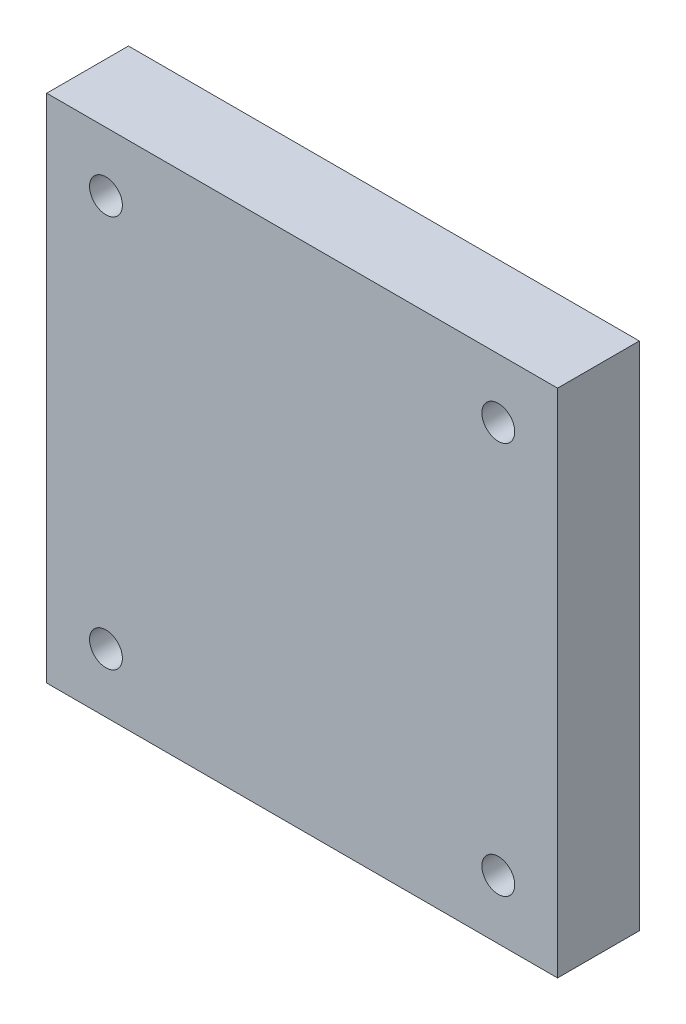
SolidWorks part; units mm, degrees
ref_plane "Front Plane" through (0, 0, 0) normal (0, 0, 1) x (1, 0, 0)
ref_plane "Top Plane" through (0, 0, 0) normal (0, 1, 0) x (1, 0, 0)
ref_plane "Right Plane" through (0, 0, 0) normal (1, 0, 0) x (0, 0, -1)
sketch "Sketch1" plane through (0, 0, 0) normal (0, 0, 1) x (1, 0, 0)
  line L0 (-38.1, 0) -> (0, 0) construction
  line L1 (0, 0) -> (-30.48, 30.48) construction
  line L3 (39.6875, -39.6875) -> (-39.6875, -39.6875)
  line L4 (39.6875, -39.6875) -> (39.6875, 39.6875)
  line L5 (39.6875, 39.6875) -> (-39.6875, 39.6875)
  line L6 (-39.6875, -39.6875) -> (-39.6875, 39.6875)
  line L7 (39.6875, -39.6875) -> (-39.6875, 39.6875) construction
  line L8 (39.6875, 39.6875) -> (-39.6875, -39.6875) construction
  circle A0 centre (0, 0) radius 38.1 construction
  circle A1 centre (-30.48, 30.48) radius 2.5527 construction
  dimension "D1" = 76.2
  dimension "D2" = 5.1054
  dimension "D4" = 1.5875
  dimension "D3" = 45
  dimension "D5" = 30.48
extrude "Boss-Extrude1" add sketch "Sketch1" along normal blind 12.7
sketch "Sketch2" plane through (0, 0, 0) normal (0, 0, -1) x (-1, 0, 0)
  circle A0 centre (0, 0) radius 38.1
  dimension "D1" = 76.2
extrude "Cut-Extrude1" cut sketch "Sketch2" against normal blind 8.89
hole_wizard "#7 (0.201) Diameter Hole1" positions "Sketch4" profile "Sketch3" hole size "#7" standard "Ansi Inch"
sketch "Sketch4" plane through (0, 0, 12.7) normal (0, 0, 1) x (1, 0, 0)
  line L0 (-30.48, 30.48) -> (30.48, -30.48) construction
  line L3 (30.48, 30.48) -> (-30.48, -30.48) construction
  point P0 (30.48, 30.48)
  point P1 (-30.48, 30.48)
  point P3 (-30.48, -30.48)
  point P5 (30.48, -30.48)
  dimension "D1" = 60.96
  dimension "D2" = 60.96
sketch "Sketch3" plane through (30.48, 30.48, 12.7) normal (1, 0, 0) x (0, -1, 0)
  line L0 (0, 0) -> (0, 33.2838)
  line L1 (0, 33.2838) -> (2.5527, 31.75)
  line L2 (2.5527, 31.75) -> (2.5527, 0)
  line L5 (2.5527, 0) -> (0, 0)
  line L10 (0, 33.2838) -> (-2.5527, 31.75) construction
  line L11 (0, -6.35) -> (0, 107.95) construction
  dimension "Hole Dia." = 5.1054
  dimension "Hole Depth" = 31.75
  dimension "Drill Angle" = 118
